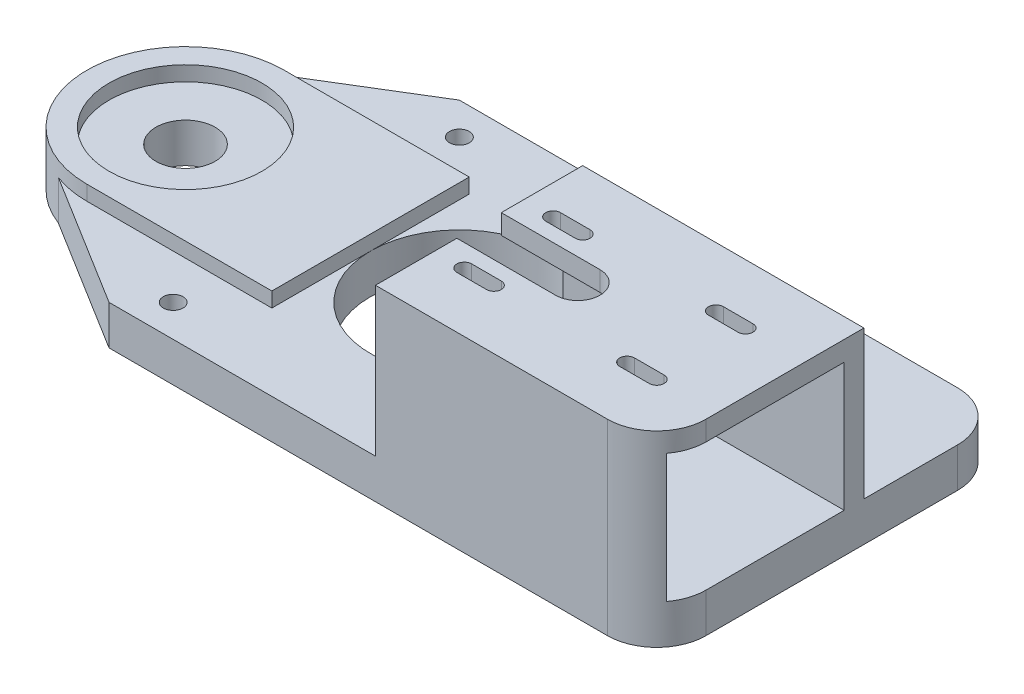
SolidWorks part; units mm, degrees
ref_plane "Front Plane" through (0, 0, 0) normal (0, 0, 1) x (1, 0, 0)
ref_plane "Top Plane" through (0, 0, 0) normal (0, 1, 0) x (1, 0, 0)
ref_plane "Right Plane" through (0, 0, 0) normal (1, 0, 0) x (0, 0, -1)
sketch "Sketch1" plane through (0, 0, 0) normal (0, 1, 0) x (1, 0, 0)
  line L0 (35.5, 0) -> (35.5, -71) construction
  line L5 (0, 0) -> (71, 0)
  line L6 (0, 0) -> (0, -71)
  line L7 (0, -71) -> (71, -71)
  line L8 (71, 0) -> (71, -71)
  line L9 (0, -35.5) -> (-20, -35.5)
  line L10 (0, 0) -> (-32.2202, -19.6675)
  line L11 (0, -71) -> (-27.0695, -54.2089)
  line L13 (71, 0) -> (111, 0)
  line L14 (71, 0) -> (71, -71)
  line L15 (71, -71) -> (111, -71)
  line L16 (111, 0) -> (111, -71)
  circle A0 centre (35.5, -35.5) radius 18
  circle A1 centre (-20, -35.5) radius 15.5
  circle A2 centre (-20, -35.5) radius 20
  circle A3 centre (-20, -35.5) radius 6
  dimension "D3" = 40
  dimension "D4" = 12
  dimension "D1" = 71
  dimension "D2" = 71
extrude "Boss-Extrude4" add sketch "Sketch1" along normal blind 8 contours L16 L13 L8 L15 | L5 L0 A0 L7 L8 | L0 L5 L6 L7 A0 | A2 L6 L10 | A2 L11 L6 | A2 L10 A1 | A3 A1 region at (55.808, 0, 35.5) region at (15.192, 0, 35.5) region at (-7.3951, 0, 13.2815) region at (91, 0, 35.5) region at (-35.0616, 0, 35.5) region at (-7.2453, 0, 57.6927) region at (-8.9504, 0, 51.4874)
sketch "Sketch5" plane through (0, 8, 0) normal (0, 1, 0) x (1, 0, 0)
  circle A0 centre (-20, -35.5) radius 15.5
  circle A1 centre (-20, -35.5) radius 20
extrude "Boss-Extrude5" add sketch "Sketch5" along normal blind 3
sketch "Sketch6" plane through (111, 0, 0) normal (1, 0, 0) x (0, 0, -1)
  line L0 (0, 8) -> (-71, 8) construction
  line L1 (-71, 8) -> (-67, 8)
  line L2 (-71, 8) -> (-71, 38)
  line L3 (-71, 38) -> (-67, 38)
  line L4 (-67, 8) -> (-67, 38)
  line L5 (-67, 38) -> (-33, 38)
  line L6 (-67, 38) -> (-67, 34)
  line L7 (-67, 34) -> (-33, 34)
  line L8 (-33, 38) -> (-33, 34)
  line L9 (-33, 38) -> (-29, 38)
  line L10 (-33, 38) -> (-33, 8)
  line L11 (-33, 8) -> (-29, 8)
  line L12 (-29, 38) -> (-29, 8)
  line M8 (0, 8) -> (-71, 8)
  dimension "D1" = 30
  dimension "D2" = 4
  dimension "D3" = 34
  dimension "D4" = 4
  dimension "D5" = 4
extrude "Boss-Extrude6" add sketch "Sketch6" against normal blind 57 contours L4 L3 L2 M8 | L8 L5 L4 L7 | L12 L9 L8 L10 M8 region at (111, 23, 69) region at (111, 36, 50) region at (111, 23, 31)
sketch "Sketch7" plane through (0, 38, 0) normal (0, 1, 0) x (1, 0, 0)
  line L0 (54, -50) -> (111, -50) construction
  line L1 (54, -71) -> (54, -29) construction
  line L2 (111, -71) -> (111, -29) construction
  line L3 (54, -50) -> (74, -50) construction
  line L4 (54, -45.5) -> (74, -45.5)
  line L5 (54, -54.5) -> (74, -54.5)
  line L6 (54, -50) -> (54, -41)
  line L7 (54, -41) -> (60, -41)
  line L8 (60, -41) -> (66, -41) construction
  line L9 (60, -39.5) -> (66, -39.5)
  line L10 (60, -42.5) -> (66, -42.5)
  line L11 (60, -59) -> (66, -59) construction
  line L12 (60, -60.5) -> (66, -60.5)
  line L13 (60, -57.5) -> (66, -57.5)
  line L14 (93, -41) -> (99, -41) construction
  line L15 (93, -39.5) -> (99, -39.5)
  line L16 (93, -42.5) -> (99, -42.5)
  line L17 (93, -59) -> (99, -59) construction
  line L18 (93, -60.5) -> (99, -60.5)
  line L19 (93, -57.5) -> (99, -57.5)
  arc A0 (54, -45.5) -> (54, -54.5) centre (54, -50) ccw
  arc A1 (74, -54.5) -> (74, -45.5) centre (74, -50) ccw
  arc A2 (60, -39.5) -> (60, -42.5) centre (60, -41) ccw
  arc A3 (66, -42.5) -> (66, -39.5) centre (66, -41) ccw
  arc A4 (60, -60.5) -> (60, -57.5) centre (60, -59) cw
  arc A5 (66, -57.5) -> (66, -60.5) centre (66, -59) cw
  arc A6 (93, -39.5) -> (93, -42.5) centre (93, -41) ccw
  arc A7 (99, -42.5) -> (99, -39.5) centre (99, -41) ccw
  arc A8 (93, -60.5) -> (93, -57.5) centre (93, -59) cw
  arc A9 (99, -57.5) -> (99, -60.5) centre (99, -59) cw
  point P6 (64, -50)
  point P14 (63, -41)
  point P23 (63, -59)
  point P30 (96, -41)
  point P39 (96, -59)
  line M14 (54, -29) -> (54, -71)
  dimension "D1" = 2
extrude "Cut-Extrude1" cut sketch "Sketch7" against normal up to next contours L5 A1 L4 M14 | L13 A5 L12 A4 | L9 A3 L10 A2 | L19 A9 L18 A8 | L16 A7 L15 A6 region at (65.7886, 38, 50)
sketch "Sketch9" plane through (0, 0, 0) normal (0, -1, 0) x (1, 0, 0)
  line L0 (-20, 35.5) -> (111, 35.5) construction
  line L1 (111, 0) -> (111, 71) construction
  line L2 (35.5, 35.5) -> (35.5, 71) construction
  line L3 (0, 71) -> (111, 71) construction
  line L5 (6.5, 6.5) -> (64.5, 6.5)
  line L6 (6.5, 6.5) -> (6.5, 64.5)
  line L7 (6.5, 64.5) -> (64.5, 64.5)
  line L8 (64.5, 6.5) -> (64.5, 64.5)
  line L9 (6.5, 6.5) -> (64.5, 64.5) construction
  line L10 (6.5, 64.5) -> (64.5, 6.5) construction
  circle A0 centre (64.5, 64.5) radius 2
  circle A1 centre (6.5, 64.5) radius 2
  circle A2 centre (6.5, 6.5) radius 2
  circle A3 centre (64.5, 6.5) radius 2
  dimension "D1" = 58
  dimension "D2" = 58
extrude "Cut-Extrude2" cut sketch "Sketch9" against normal up to next contours A0 | A1 | A3 | A2
sketch "Sketch10" plane through (0, 8, 0) normal (0, 1, 0) x (1, 0, 0)
  line L1 (-20, -15.5) -> (17.5, -15.5)
  line L2 (-20, -15.5) -> (-20, -55.5)
  line L3 (-20, -55.5) -> (17.5, -55.5)
  line L4 (17.5, -15.5) -> (17.5, -55.5)
  arc A0 (-27.0695, -54.2089) -> (-28.4961, -17.3943) centre (-20, -35.5) ccw construction
  circle A1 centre (-20, -35.5) radius 20 construction
  circle A2 centre (-20, -35.5) radius 20
  arc M17 (-28.4961, -17.3943) -> (-27.0695, -54.2089) centre (-20, -35.5) cw
extrude "Boss-Extrude8" add sketch "Sketch10" along normal blind 3 contours L4 L1 L3 M17 region at (6.1468, 8, 35.5)
fillet "Fillet1" radius 10 1 edges at (111, 19, 71) type face fillet first side face at (111, 15.3333, 33.3333) second side face at (55, 15.3333, 71)
fillet "Fillet2" radius 10 1 edges at (111, 4, 0) type face fillet first side face at (55.5, 4, 0) second side face at (111, 17.6, 36.8)
